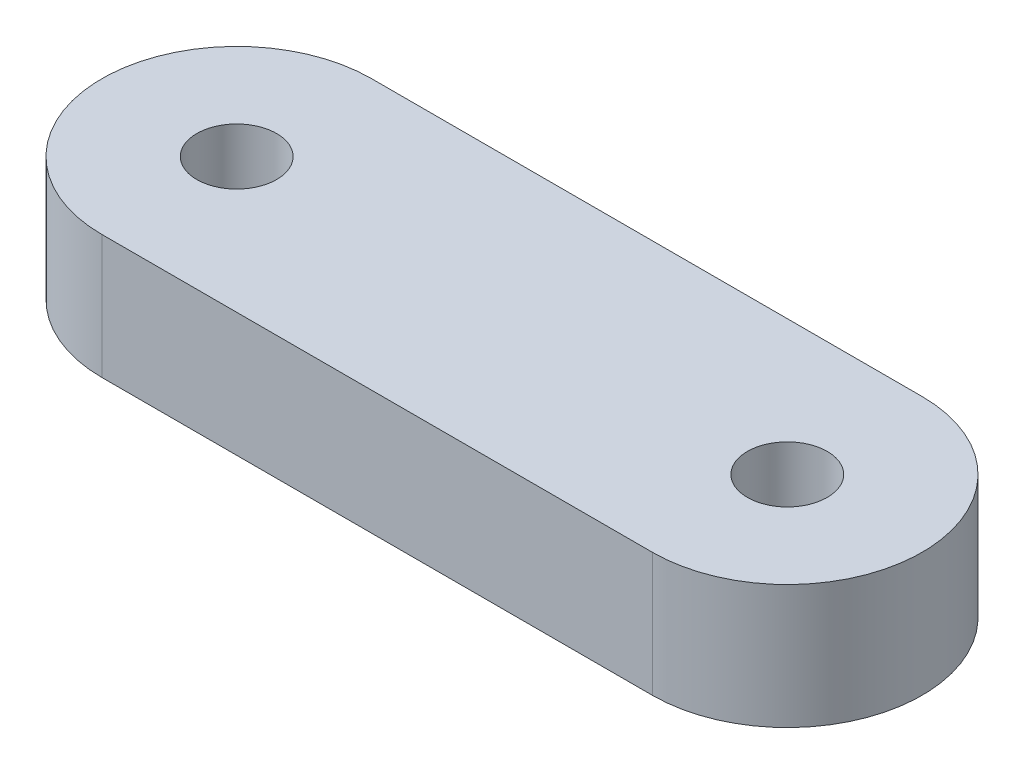
SolidWorks part; units mm, degrees
ref_plane "Front Plane" through (0, 0, 0) normal (0, 0, 1) x (1, 0, 0)
ref_plane "Top Plane" through (0, 0, 0) normal (0, 1, 0) x (1, 0, 0)
ref_plane "Right Plane" through (0, 0, 0) normal (1, 0, 0) x (0, 0, -1)
sketch "Sketch1" plane through (0, 0, 0) normal (0, 1, 0) x (1, 0, 0)
  line L0 (14.9, 0) -> (14.9, 15.5804) construction
  line L1 (-10, 4.9) -> (10, 4.9)
  line L2 (-14.9, 0) -> (-14.9, 15.5804) construction
  line L3 (-10, -4.9) -> (10, -4.9)
  line L4 (-10, 4.9) -> (-10, -4.9) construction
  line L5 (-10, 4.9) -> (10, -4.9) construction
  line L6 (-10, -4.9) -> (10, 4.9) construction
  line L7 (10, 4.9) -> (10, -4.9) construction
  line L8 (0, 4.9) -> (0, -4.9) construction
  arc A0 (-10, 4.9) -> (-10, -4.9) centre (-10, 0) ccw
  arc A1 (10, -4.9) -> (10, 4.9) centre (10, 0) ccw
  circle A2 centre (-10, 0) radius 1.45
  circle A3 centre (10, 0) radius 1.45
  point P0 (0, 0)
  dimension "D4" = 4.9
  dimension "D5" = 2.9
  dimension "D1" = 9.8
  dimension "D2" = 20
extrude "Boss-Extrude1" add sketch "Sketch1" along normal blind 4.5
equation "\"Y-ROD-SPACING\"=75"
equation "\"Y-BED-OFFSET\"=2"
equation "\"Y-BED-ROD-INSET\"=3.5"
equation "\"T-SLOT-NUT-FILLET-RADIUS\"=0.5"
equation "\"T-SLOT-SCREW-SHAFT-RADIUS\"=1.55"
equation "\"T-SLOT-SCREW-SHAFT-CUTOUT-LENGTH\"=11"
equation "\"T-SLOT-NUT-DEPTH\"=3.5"
equation "\"T-SLOT-NUT-WIDTH\"=2.85"
equation "\"T-SLOT-NUT-END-DISTANCE\"=8"
equation "\"ACRYLIC-TAB-CUTOUT-SIZE\"=\"ACRYLIC-THICKNESS\"+\"ACRYLIC-TAB-TOLERANCE\"*2"
equation "\"ACRYLIC-M3-HOLE\"=2.9"
equation "\"D5@Sketch1\"=\"ACRYLIC-M3-HOLE\""
equation "\"SMOOTHROD-CAP-SCREW-DISTANCE\"=20"
equation "\"D2@Sketch1\"=\"SMOOTHROD-CAP-SCREW-DISTANCE\""
equation "\"X-ROD-SPACING\"=45"
equation "\"Z-ROD-SPACING\"=17.5"
equation "\"ACRYLIC-THICKNESS\"=10"
equation "\"ACRYLIC-THICKNESS2\"=4.5"
equation "\"ACRYLIC-TAB-WIDTH\"=\"ACRYLIC-THICKNESS\""
equation "\"FRAME-WIDTH-INNER\"=370"
equation "\"NEMA17-HOLE-SPACING\"=31"
equation "\"NEMA17-CENTRAL-CUTOUT\"=22.5"
equation "\"Z-BRACKET-REACH\"=55"
equation "\"TOP-BRACKET-SPACING\"=40"
equation "\"SMOOTHROD-X-LENGTH\"=350"
equation "\"SMOOTHROD-Y-LENGTH\"=350"
equation "\"SMOOTHROD-Z-LENGTH\"=350"
equation "\"SMOOTHROD-TIGHTENING-HEADROOM\"=.25"
equation "\"LEADSCREW-Z-LENGTH\"=300"
equation "\"SCREW-LENGTH-FRAME\"=\"ACRYLIC-THICKNESS\" + 10"
equation "\"SCREW-HEAD-RADIUS\"=6"
equation "\"PRINTED-X-SMOOTHROD-DIAMETER\"=9.0"
equation "\"PRINTED-X-SMOOTHROD-CUTOUT\"=10"
equation "\"PRINTED-X-BASE-HEIGHT\"=10"
equation "\"PRINTED-LM8UU-CUTOUT-SIZE\"=15.5"
equation "\"PRINTED-LM8UU-CUTOUT-LENGTH\"=24.5"
equation "\"PRINTED-X-IDLER-HEIGHT\"=16"
equation "\"PSU-MOUNTING-WIDTH\"=95"
equation "\"PSU-MOUNTING-HEIGHT\"=177"
equation "\"D1@Boss-Extrude1\"=\"ACRYLIC-THICKNESS2\""
